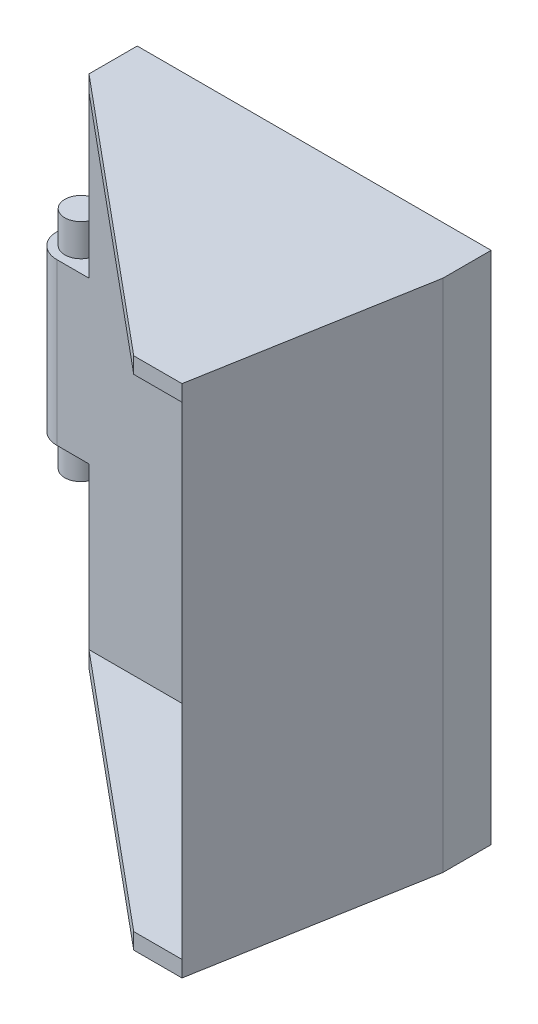
SolidWorks part; units mm, degrees
ref_plane "前视基准面" through (0, 0, 0) normal (0, 0, 1) x (1, 0, 0)
ref_plane "上视基准面" through (0, 0, 0) normal (0, 1, 0) x (1, 0, 0)
ref_plane "右视基准面" through (0, 0, 0) normal (1, 0, 0) x (0, 0, -1)
sketch "草图1" plane through (0, 0, 0) normal (0, 1, 0) x (1, 0, 0)
  line L0 (0, 0) -> (120, 0)
  line L1 (0, 15) -> (120, 15)
  line L7 (120, 15) -> (120, 0)
  arc A1 (0, 0) -> (0, 15) centre (0, 7.5) cw
  circle A3 centre (0, 7.5) radius 5
extrude "凸台-拉伸1" add sketch "草图1" along normal blind 42.5 and the other way blind 7.5
ref_plane "基准面4" through (0, 17.5, 0) normal (0, 1, 0) x (1, 0, 0)
sketch "草图2" plane through (0, 0, 0) normal (0, 1, 0) x (1, 0, 0)
  circle A0 centre (0, 7.5) radius 5
extrude "凸台-拉伸2" add sketch "草图2" against normal mid plane 35
ref_plane "基准面5" through (0, 17.5, 0) normal (0, 1, 0) x (1, 0, 0)
ref_plane "基准面6" through (0, 52.5, 0) normal (0, 1, 0) x (1, 0, 0)
sketch "草图3" plane through (0, 0, 0) normal (0, 1, 0) x (1, 0, 0)
  circle A0 centre (0, 7.5) radius 5
extrude "凸台-拉伸3" add sketch "草图3" along normal up to surface (52.5 mm away) up to plane "基准面6"
ref_plane "基准面7" through (0, 27.5, 0) normal (0, -1, 0) x (-1, 0, 0)
ref_plane "基准面8" through (0, 7.5, 0) normal (0, 1, 0) x (1, 0, 0)
ref_plane "基准面9" through (10, 0, 0) normal (1, 0, 0) x (0, 0, -1)
sketch "草图5" plane through (0, 0, 0) normal (0, 1, 0) x (1, 0, 0)
  line L1 (10, 0) -> (120, 0)
  line L2 (10, 0) -> (10, 15)
  line L3 (10, 15) -> (120, 15)
  line L4 (120, 0) -> (120, 15)
extrude "凸台-拉伸4" add sketch "草图5" along normal blind 97.5 and the other way blind 62.5 contours L1 L4 L3 L2
sketch "草图9" plane through (0, 97.5, 0) normal (0, 1, 0) x (1, 0, 0)
  line L1 (107.8446, -68.9365) -> (92.8446, -68.9365)
  line L2 (92.8446, -68.9365) -> (105, 0)
  line L3 (10, 0) -> (120, 0) construction
  line L4 (105, 0) -> (120, 0)
  line L5 (120, 0) -> (107.8446, -68.9365)
extrude "凸台-拉伸6" add sketch "草图9" against normal up to surface (160 mm away) up to face at (65, -62.5, -7.5)
sketch "草图11" plane through (0, 97.5, 0) normal (0, 1, 0) x (1, 0, 0)
  line L0 (92.8446, -68.9365) -> (10, 0)
  line L1 (10, 0) -> (105, 0)
  line L2 (105, 0) -> (92.8446, -68.9365)
extrude "凸台-拉伸7" add sketch "草图11" against normal blind 5
sketch "草图12" plane through (0, -62.5, 0) normal (0, -1, 0) x (1, 0, 0)
  line L0 (10, 0) -> (92.8446, 68.9365)
  line L1 (92.8446, 68.9365) -> (105, 0)
  line L2 (105, 0) -> (10, 0)
extrude "凸台-拉伸8" add sketch "草图12" against normal blind 5
chamfer "倒角1" distance 15 angle 85 1 edges at (92.8446, 17.5, 68.9365) first distance on face at (97.8446, 17.5, 68.9365)
fillet "圆角1" radius 10 1 edges at (105, 17.5, 0)
